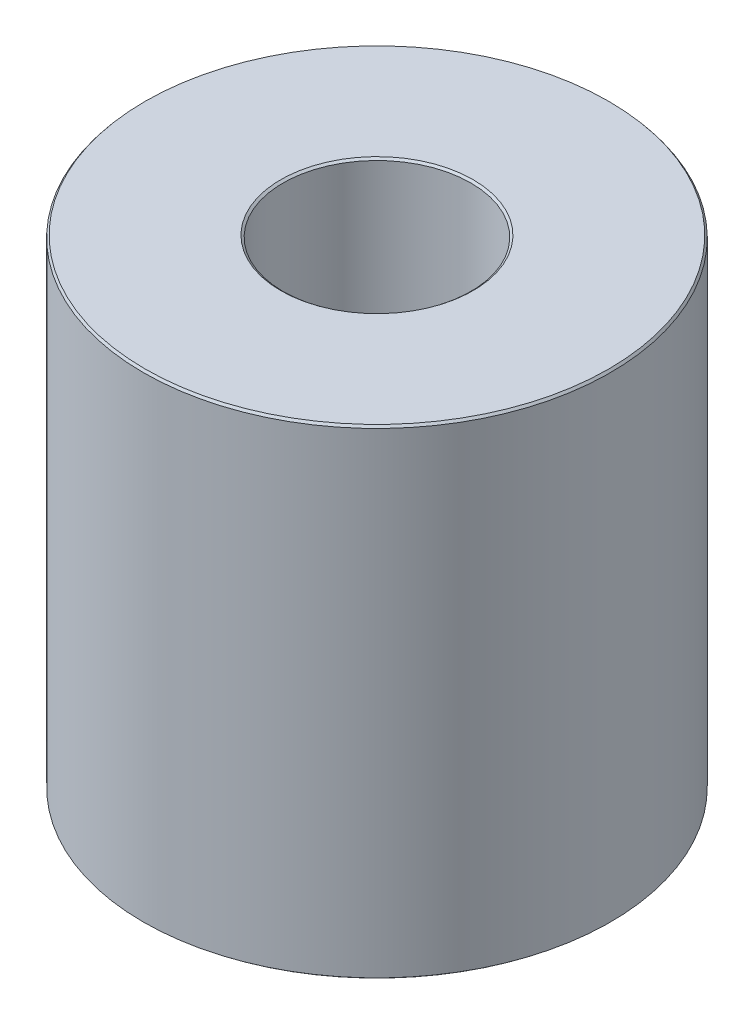
SolidWorks part; units mm, degrees
ref_plane "Front Plane" through (0, 0, 0) normal (0, 0, 1) x (1, 0, 0)
ref_plane "Top Plane" through (0, 0, 0) normal (0, 1, 0) x (1, 0, 0)
ref_plane "Right Plane" through (0, 0, 0) normal (1, 0, 0) x (0, 0, -1)
sketch "Sketch1" plane through (0, 0, 0) normal (0, 1, 0) x (1, 0, 0)
  circle A0 centre (0, 0) radius 32.5
  dimension "SLEEVE_OD" = 65
extrude "Boss-Extrude1" add sketch "Sketch1" along normal blind 66.7669
sketch "Sketch2" plane through (0, 0, 0) normal (0, 1, 0) x (1, 0, 0)
  circle A0 centre (0, 0) radius 13.0702
  dimension "BORE_D" = 26.1403
extrude "Cut-Extrude1" cut sketch "Sketch2" along normal through all
chamfer "Chamfer1" distance 0.3136 angle 38.018 4 edges at (0, 66.7669, 13.0702) (0, 0, 13.0702) (0, 0, 32.5) (0, 66.7669, 32.5) first distance on face at (0, 66.7669, 13.0702) first distance on face at (0, 0, 13.0702) first distance on face at (0, 66.7669, 32.5)
